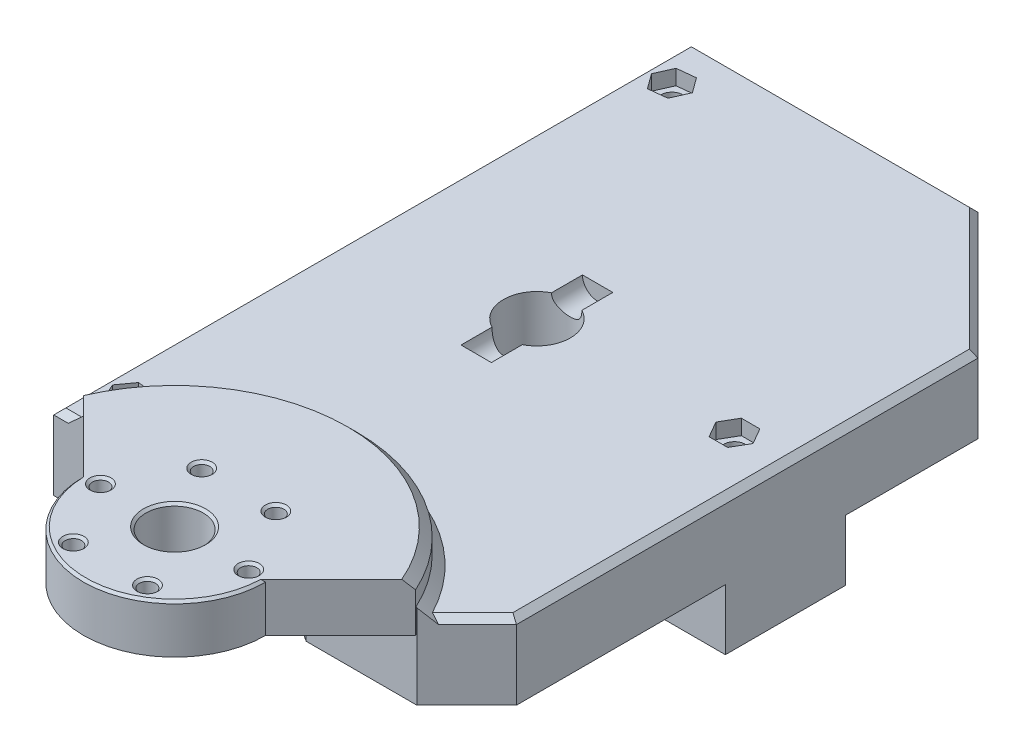
SolidWorks part; units mm, degrees
ref_plane "Front Plane" through (0, 0, 0) normal (0, 0, 1) x (1, 0, 0)
ref_plane "Top Plane" through (0, 0, 0) normal (0, 1, 0) x (1, 0, 0)
ref_plane "Right Plane" through (0, 0, 0) normal (1, 0, 0) x (0, 0, -1)
sketch "Sketch1" plane through (0, 0, 0) normal (0, 1, 0) x (1, 0, 0)
  line L1 (-43.18, 66.675) -> (43.18, 66.675)
  line L2 (-43.18, 66.675) -> (-43.18, -66.675)
  line L3 (-43.18, -66.675) -> (43.18, -66.675)
  line L4 (43.18, 66.675) -> (43.18, -66.675)
  line L5 (-43.18, 66.675) -> (43.18, -66.675) construction
  line L6 (-43.18, -66.675) -> (43.18, 66.675) construction
  point P0 (0, 0)
  dimension "D1" = 86.36
  dimension "D2" = 133.35
extrude "Boss-Extrude1" add sketch "Sketch1" along normal blind 15.875
sketch "Sketch2" plane through (0, 0, 0) normal (0, -1, 0) x (1, 0, 0)
  line L0 (43.18, 66.675) -> (43.18, -66.675) construction
  line L1 (-43.18, -12.573) -> (43.18, -12.573)
  line L2 (-43.18, -12.573) -> (-43.18, 12.573)
  line L3 (-43.18, 12.573) -> (43.18, 12.573)
  line L4 (43.18, -12.573) -> (43.18, 12.573)
  line L5 (-43.18, -12.573) -> (43.18, 12.573) construction
  line L6 (-43.18, 12.573) -> (43.18, -12.573) construction
  point P0 (0, 0)
  dimension "D1" = 25.146
extrude "Boss-Extrude2" add sketch "Sketch2" along normal blind 12.7
sketch "Sketch3" plane through (0, 15.875, 0) normal (0, 1, 0) x (1, 0, 0)
  line L0 (43.18, 0) -> (-2.032, 0)
  line L1 (43.18, -66.675) -> (43.18, 66.675) construction
  line L2 (-2.032, 0) -> (-2.032, -82.55)
  line L3 (-43.18, -66.675) -> (43.18, -66.675) construction
  line L4 (-43.18, 66.675) -> (-43.18, -66.675) construction
  circle A0 centre (-2.032, -82.55) radius 19.05
  circle A1 centre (-2.032, -82.55) radius 38.1
  circle A2 centre (-37.338, -56.769) radius 3.175
  dimension "D3" = 76.2
  dimension "D4" = 9.906
  dimension "D6" = 6.35
  dimension "D1" = 45.212
  dimension "D2" = 82.55
  dimension "D5" = 5.842
ref_plane "Plane1" through (0, 19.05, 0) normal (0, -1, 0) x (-1, 0, 0)
sketch "Sketch5" plane through (0, 19.05, 0) normal (0, -1, 0) x (-1, 0, 0)
  line L0 (-17.018, -82.55) -> (-32.893, -66.675)
  line L1 (43.18, -66.675) -> (-43.18, -66.675) construction
  line L2 (21.082, -82.55) -> (36.7578, -66.8742)
  arc A0 (-17.018, -82.55) -> (21.082, -82.55) centre (2.032, -82.55) ccw
  arc A1 (36.7578, -66.8742) -> (-32.6938, -66.8742) centre (2.032, -82.55) ccw
  circle A2 centre (2.032, -82.55) radius 6
  circle A3 centre (2.032, -82.55) radius 15.5
  circle A4 centre (17.532, -82.55) radius 1.7
  circle A5 centre (9.782, -95.9734) radius 1.7
  circle A6 centre (-5.718, -95.9734) radius 1.7
  circle A7 centre (-13.468, -82.55) radius 1.7
  circle A8 centre (-5.718, -69.1266) radius 1.7
  circle A9 centre (9.782, -69.1266) radius 1.7
  point P25 (2.032, -82.55)
  dimension "D1" = 6
  dimension "D2" = 3.4
extrude "Boss-Extrude3" add sketch "Sketch5" against normal blind 3.81 separate body contours L2 A1 L0 A0 A9 A3 A4 A5 A6 A7 A8 | A9 A3 A8 A7 A6 A5 A4 A2 region at (-2.032, 19.05, 65.0957) region at (-15.3949, 19.05, 82.55)
sketch "Sketch6" plane through (0, 0, 0) normal (0, -1, 0) x (1, 0, 0)
  circle A0 centre (-2.032, 82.55) radius 19.685
extrude "Cut-Extrude1" cut sketch "Sketch6" against normal up to surface (19.05 mm away) up to plane "Plane1"
chamfer "Chamfer2" distance 0.508 angle 45 8 edges at (-2.032, 22.86, 101.6) (-9.782, 22.86, 67.4266) (-17.532, 22.86, 80.85) (-9.782, 22.86, 94.2734) (5.718, 22.86, 94.2734) (13.468, 22.86, 80.85) (5.718, 22.86, 67.4266) (-2.032, 22.86, 76.55)
extrude "Boss-Extrude4" add sketch "Sketch5<4>" along normal blind 6.35 contours L2 A1 L0 A0 A9 A3 A4 A5 A6 A7 A8 | A9 A3 A8 A7 A6 A5 A4 A2 region at (-2.032, 19.05, 65.0957) region at (-15.3949, 19.05, 82.55)
sketch "Sketch5<4>" plane through (0, 19.05, 0) normal (0, -1, 0) x (-1, 0, 0) same geometry as "Sketch5"
chamfer "Chamfer1" distance 1.905 angle 45 2 edges at (-2.032, 22.86, 44.45) (-2.032, 15.875, 44.45)
sketch "Sketch7" plane through (0, 15.875, 0) normal (0, 1, 0) x (1, 0, 0)
  circle A0 centre (-37.338, -56.769) radius 5.08
extrude "Cut-Extrude2" cut sketch "Sketch7" along normal blind 6.35
sketch "Sketch8" plane through (0, 15.875, 0) normal (0, 1, 0) x (1, 0, 0)
  line L0 (-34.7739, -58.6414) -> (-34.62, -58.7537)
  line L1 (-35.4656, -54.2049) -> (-35.0462, -53.6305)
  line L2 (-19.558, 0) -> (19.558, 0) construction
  line L3 (-35.0462, -53.6305) -> (-38.9101, -53.215)
  line L4 (-38.9101, -53.215) -> (-41.2019, -56.3535)
  line L5 (-41.2019, -56.3535) -> (-39.6298, -59.9075)
  line L6 (-39.6298, -59.9075) -> (-35.7659, -60.323)
  line L7 (-35.7659, -60.323) -> (-33.4741, -57.1845)
  line L8 (-33.4741, -57.1845) -> (-35.0462, -53.6305)
  line L9 (-35.7659, 60.323) -> (-33.4741, 57.1845)
  line L10 (-39.6298, 59.9075) -> (-35.7659, 60.323)
  line L11 (-41.2019, 56.3535) -> (-39.6298, 59.9075)
  line L12 (-38.9101, 53.215) -> (-41.2019, 56.3535)
  line L13 (-35.0462, 53.6305) -> (-38.9101, 53.215)
  line L14 (-33.4741, 57.1845) -> (-35.0462, 53.6305)
  line L15 (43.18, 0) -> (-2.032, 0) construction
  line L16 (28.6259, 0) -> (30.5689, -3.3655)
  line L17 (30.5689, -3.3655) -> (34.4551, -3.3655)
  line L18 (34.4551, -3.3655) -> (36.3981, 0)
  line L19 (36.3981, 0) -> (34.4551, 3.3655)
  line L20 (34.4551, 3.3655) -> (30.5689, 3.3655)
  line L21 (30.5689, 3.3655) -> (28.6259, 0)
  circle A1 centre (-37.338, -56.769) radius 3.3655 construction
  circle A2 centre (32.512, 0) radius 3.3655 construction
  circle A3 centre (-37.338, -56.769) radius 2.2225
  circle A4 centre (32.512, 0) radius 2.2225
  circle A5 centre (-37.338, 56.769) radius 2.2225
  dimension "D1" = 69.85
extrude "Cut-Extrude3" cut sketch "Sketch8" against normal blind 3.175 contours L14 L9 L10 L11 L12 L13 | L20 L21 L16 L17 L18 L19 | A5 | A4 | L7 L8 L3 L4 L5 L6 A3 | A3 region at (-34.3562, 15.875, 55.45) region at (-34.7048, 15.875, -58.6918) region at (29.6864, 15.875, -1.6313) region at (-37.338, 15.875, 56.769) region at (32.512, 15.875, 0) region at (-37.338, 15.875, -56.769)
extrude "Cut-Extrude4" cut sketch "Sketch8<3>" against normal through all both and the other way through all contours A3 | A5 | A4 region at (-37.338, 15.875, 56.769) region at (-37.338, 15.875, -56.769)
sketch "Sketch8<3>" plane through (0, 15.875, 0) normal (0, 1, 0) x (1, 0, 0) same geometry as "Sketch8"
sketch "Sketch10" plane through (0, 15.875, 0) normal (0, 1, 0) x (1, 0, 0)
  circle A0 centre (-8.8079, 0) radius 6.985
  point P2 (-8.8079, 0)
extrude "Cut-Extrude5" cut sketch "Sketch10" against normal through all both and the other way through all
sketch "Sketch11" plane through (0, 0, 0) normal (0, 0, 1) x (1, 0, 0)
  line L0 (36.068, 15.875) -> (-40.132, 15.875) construction
  line L1 (17.018, 15.875) -> (-21.082, 15.875) construction
  circle A0 centre (-8.807, 15.875) radius 3.175
extrude "Cut-Extrude6" cut sketch "Sketch11" against normal blind 12.7 and the other way blind 12.7
chamfer "Chamfer3" distance 26.416 angle 45 1 edges at (43.18, 7.9375, -66.675)
chamfer "Chamfer4" distance 10.414 angle 45 1 edges at (43.18, 7.9375, 66.675)
sketch "Sketch13" plane through (0, -12.7, 0) normal (0, -1, 0) x (1, 0, 0)
  circle A0 centre (-8.8079, 0) radius 19.05
  dimension "D1" = 38.1
extrude "Cut-Extrude7" cut sketch "Sketch13" against normal up to surface (12.7 mm away) up to face at (-37.338, 0, 58.9915)
chamfer "Chamfer5" distance 1.27 angle 45 6 edges at (38.634, 15.875, 60.807) (-40.9662, 15.875, 66.675) (-43.18, 15.875, 0) (-13.208, 15.875, -66.675) (29.972, 15.875, -53.467) (43.18, 15.875, 8.001)
